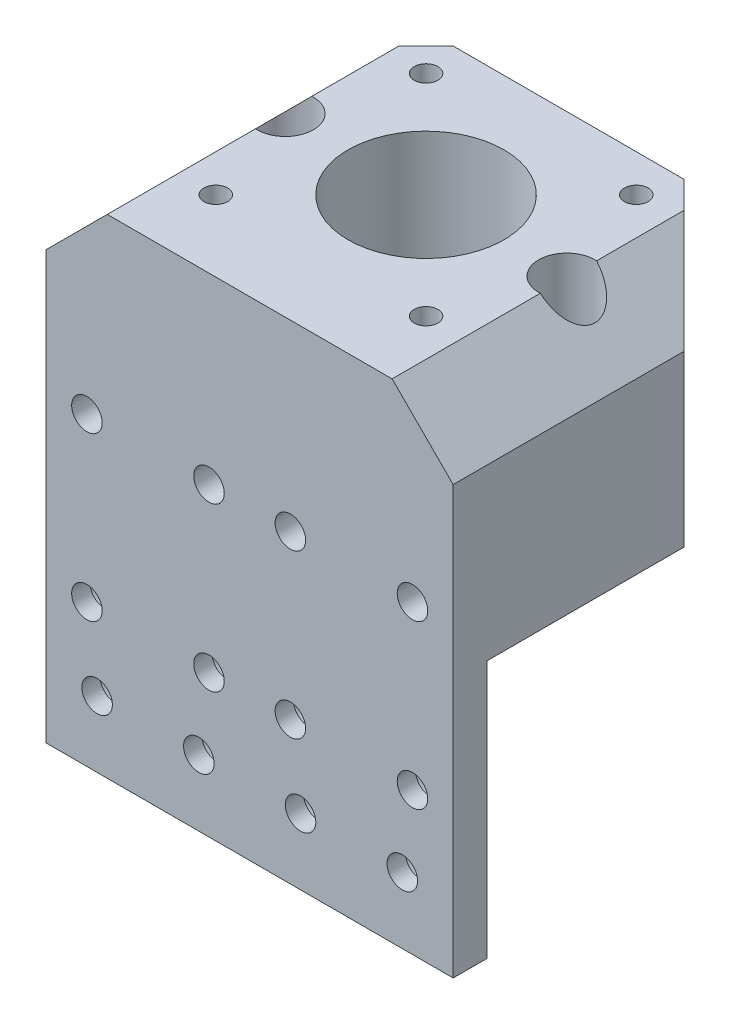
SolidWorks part; units mm, degrees
ref_plane "Front Plane" through (0, 0, 0) normal (0, 0, 1) x (1, 0, 0)
ref_plane "Top Plane" through (0, 0, 0) normal (0, 1, 0) x (1, 0, 0)
ref_plane "Right Plane" through (0, 0, 0) normal (1, 0, 0) x (0, 0, -1)
sketch "Sketch2" plane through (0, 0, 0) normal (1, 0, 0) x (0, 0, -1)
  line L0 (10.5, 7) -> (15.5, 7)
  line L23 (10.5, 57) -> (15.5, 57)
  line L24 (10.5, 57) -> (10.5, 7)
  line L26 (15.5, 57) -> (15.5, 7)
  dimension "D1" = 50
  dimension "D2" = 7
  dimension "D3" = 10.5
  dimension "D4" = 5
extrude "Boss-Extrude1" add sketch "Sketch2" along normal mid plane 60 contours L0 L26 L23 L24
sketch "Sketch3" plane through (0, 0, -10.5) normal (0, 0, 1) x (1, 0, 0)
  line L0 (30, 7) -> (-30, 7) construction
  line L1 (-30, 57) -> (-30, 7) construction
  line L2 (30, 57) -> (-30, 57) construction
  line L3 (0, 57) -> (0, 7) construction
  circle A0 centre (-22.5, 16.75) radius 2.25
  circle A1 centre (-7.5, 16.75) radius 2.25
  circle A2 centre (7.5, 16.75) radius 2.25
  circle A3 centre (22.5, 16.75) radius 2.25
  circle A4 centre (-24, 52) radius 2.25
  circle A5 centre (-6, 52) radius 2.25
  circle A6 centre (-24, 28) radius 2.25
  circle A7 centre (-6, 28) radius 2.25
  circle A8 centre (6, 28) radius 2.25
  circle A9 centre (24, 28) radius 2.25
  circle A10 centre (6, 52) radius 2.25
  circle A11 centre (24, 52) radius 2.25
  dimension "D1" = 9.75
  dimension "D2" = 4.5
  dimension "D3" = 7.5
  dimension "D5" = 15
  dimension "D6" = 6
  dimension "D7" = 5
  dimension "D8" = 4.5
  dimension "D10" = 18
  dimension "D12" = 24
  dimension "D4" = 4
  dimension "D9" = 2
  dimension "D11" = 2
extrude "Cut-Extrude1" cut sketch "Sketch3" against normal up to next
sketch "Sketch6" plane through (30, 0, 0) normal (1, 0, 0) x (0, 0, -1)
  line L0 (10.5, 57) -> (10.5, 7) construction
  line L1 (10.5, 45) -> (57.5, 45)
  line L2 (10.5, 45) -> (10.5, 79)
  line L3 (10.5, 79) -> (57.5, 79)
  line L4 (57.5, 45) -> (57.5, 79)
  line L5 (10.5, 57) -> (15.5, 57) construction
  dimension "D1" = 12
  dimension "D2" = 22
  dimension "D3" = 47
extrude "Boss-Extrude3" add sketch "Sketch6" against normal up to surface (60 mm away) up to face at (-30, 32, -13)
sketch "Sketch7" plane through (0, 0, -15.5) normal (0, 0, -1) x (-1, 0, 0)
  line L0 (0, 7) -> (0, 45) construction
  line L1 (-30, 7) -> (30, 7) construction
  line L2 (30, 45) -> (-30, 45) construction
  circle A0 centre (22.5, 16.75) radius 4
  circle A1 centre (24, 28) radius 4
  circle A2 centre (7.5, 16.75) radius 4
  circle A3 centre (-7.5, 16.75) radius 4
  circle A4 centre (-22.5, 16.75) radius 4
  circle A5 centre (6, 28) radius 4
  circle A6 centre (-6, 28) radius 4
  circle A7 centre (-24, 28) radius 4
  dimension "D1" = 8
  dimension "D2" = 8
  dimension "D4" = 15
  dimension "D6" = 18
  dimension "D3" = 4
  dimension "D5" = 2
extrude "Cut-Extrude2" cut sketch "Sketch7" against normal blind 2.3
sketch "Sketch8" plane through (0, 45, 0) normal (0, -1, 0) x (1, 0, 0)
  line L0 (0, -15.5) -> (0, -57.5) construction
  line L1 (30, -15.5) -> (-30, -15.5) construction
  line L2 (-30, -57.5) -> (30, -57.5) construction
  line L3 (-30, -36.5) -> (30, -36.5) construction
  line L4 (-30, -57.5) -> (-30, -15.5) construction
  line L5 (30, -15.5) -> (30, -57.5) construction
  circle A0 centre (0, -36.5) radius 11.5
  circle A1 centre (-20.75, -36.5) radius 4.15
  circle A2 centre (20.75, -36.5) radius 4.15
  circle A3 centre (-15.5, -52) radius 1.75
  circle A4 centre (15.5, -52) radius 1.75
  circle A5 centre (15.5, -21) radius 1.75
  circle A6 centre (-15.5, -21) radius 1.75
  dimension "D1" = 23
  dimension "D2" = 8.3
  dimension "D3" = 20.75
  dimension "D4" = 3.5
  dimension "D5" = 15.5
  dimension "D6" = 15.5
extrude "Cut-Extrude3" cut sketch "Sketch8" against normal up to next
chamfer "Chamfer1" distance 13 angle 45 2 edges at (30, 62, -57.5) (-30, 62, -57.5)
sketch "Sketch9" plane through (0, 45, 0) normal (0, -1, 0) x (1, 0, 0)
  line L0 (0, -15.5) -> (0, -57.5) construction
  line L1 (30, -15.5) -> (-30, -15.5) construction
  line L2 (-17, -57.5) -> (17, -57.5) construction
  circle A0 centre (-15.5, -21) radius 3
  circle A1 centre (-15.5, -52) radius 3
  circle A2 centre (15.5, -52) radius 3
  circle A3 centre (15.5, -21) radius 3
  dimension "D1" = 6
  dimension "D3" = 31
  dimension "D2" = 2
extrude "Cut-Extrude4" cut sketch "Sketch9" against normal blind 17
chamfer "Chamfer2" distance 9 angle 45 2 edges at (30, 79, -27.5) (-30, 79, -27.5)
extrude "Cut-Extrude5" cut sketch "Sketch3<2>" against normal up to surface (5 mm away) up to face at (-24, 32, -15.5)
sketch "Sketch3<2>" plane through (0, 0, -10.5) normal (0, 0, 1) x (1, 0, 0) same geometry as "Sketch3"
